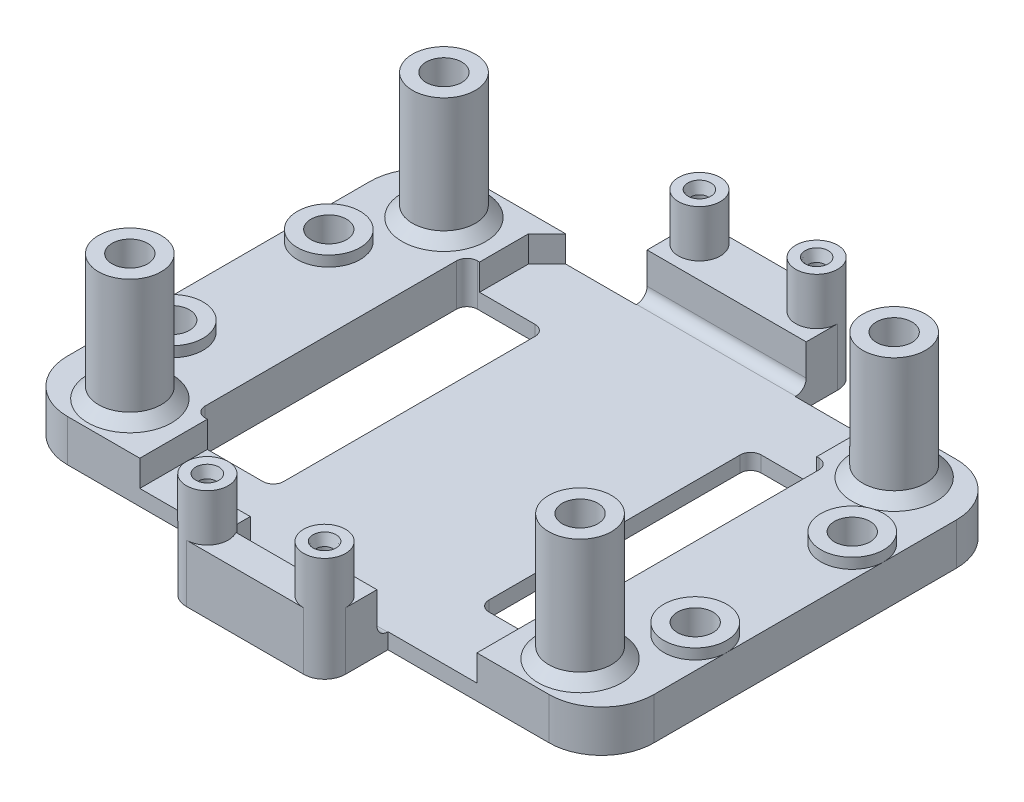
SolidWorks part; units mm, degrees
ref_plane "Front Plane" through (0, 0, 0) normal (0, 0, 1) x (1, 0, 0)
ref_plane "Top Plane" through (0, 0, 0) normal (0, 1, 0) x (1, 0, 0)
ref_plane "Right Plane" through (0, 0, 0) normal (1, 0, 0) x (0, 0, -1)
sketch "Sketch1" plane through (0, 0, 0) normal (0, 1, 0) x (1, 0, 0)
  line L0 (-15.6, 17.4701) -> (-13.6201, 19.45)
  line L1 (-13.6201, 19.45) -> (13.6201, 19.45)
  line L2 (-15.6, 17.4701) -> (-15.6, -19.45)
  line L3 (-15.6, -19.45) -> (15.6, -19.45)
  line L4 (15.6, 17.4701) -> (15.6, -19.45)
  line L5 (-14.7188, 18.3513) -> (15.6, -19.45) construction
  line L6 (-15.6, -19.45) -> (14.7188, 18.3513) construction
  line L7 (-13.6201, 19.45) -> (13.6201, 19.45)
  line L8 (13.6201, 19.45) -> (15.6, 17.4701)
  point P0 (0, 0)
  dimension "D1" = 31.2
  dimension "D2" = 38.9
  dimension "D3" = 45
  dimension "D4" = 2.8
  dimension "D5" = 2.8
  dimension "D6" = 19.45
  dimension "D7" = 15.6
sketch "Sketch2" plane through (0, 0, 0) normal (0, 1, 0) x (1, 0, 0)
  line L1 (-25, 7.5) -> (25, 7.5) construction
  line L2 (-25, 7.5) -> (-25, -7.5) construction
  line L3 (-25, -7.5) -> (25, -7.5) construction
  line L4 (25, 7.5) -> (25, -7.5) construction
  line L5 (-25, 7.5) -> (25, -7.5) construction
  line L6 (-25, -7.5) -> (25, 7.5) construction
  circle A0 centre (-25, 7.5) radius 1.7
  circle A1 centre (-25, -7.5) radius 1.7
  circle A2 centre (25, -7.5) radius 1.7
  circle A3 centre (25, 7.5) radius 1.7
  circle A4 centre (-25, 7.5) radius 3
  circle A5 centre (-25, -7.5) radius 3
  circle A6 centre (25, -7.5) radius 3
  circle A7 centre (25, 7.5) radius 3
  point P0 (0, 0)
  dimension "D3" = 3.4
  dimension "D4" = 6
  dimension "D1" = 50
  dimension "D2" = 15
extrude "Boss-Extrude1" add sketch "Sketch2" along normal blind 5
sketch "Sketch3" plane through (0, 0, 0) normal (0, 1, 0) x (1, 0, 0)
  line L0 (-13.6201, 19.45) -> (13.6201, 19.45) construction
  line L1 (-28, -19.45) -> (28, -19.45)
  line L2 (-28, -19.45) -> (-28, 19.45)
  line L3 (-28, 19.45) -> (28, 19.45)
  line L4 (28, -19.45) -> (28, 19.45)
  line L5 (-28, -19.45) -> (28, 19.45) construction
  line L6 (-28, 19.45) -> (28, -19.45) construction
  circle A0 centre (-25, 7.5) radius 3 construction
  circle A1 centre (-25, 7.5) radius 1.7 construction
  circle A2 centre (-25, 7.5) radius 1.7
  circle A3 centre (25, 7.5) radius 1.7 construction
  circle A4 centre (25, -7.5) radius 1.7 construction
  circle A5 centre (-25, -7.5) radius 1.7 construction
  circle A6 centre (25, 7.5) radius 1.7
  circle A7 centre (25, -7.5) radius 1.7
  circle A8 centre (-25, -7.5) radius 1.7
  point P0 (0, 0)
extrude "Boss-Extrude2" add sketch "Sketch3" along normal blind 4
fillet "Fillet1" radius 5 4 edges at (-28, 2, -19.45) (28, 2, -19.45) (28, 2, 19.45) (-28, 2, 19.45)
extrude "Cut-Extrude2" cut sketch "Sketch1" against normal blind 2.5 from surface contours L8 L1 L0 L2 L3 L4 region at (0, 0, 0.0609) starting at face at (0, 4, -0.75)
sketch "Sketch4" plane through (0, 4, 0) normal (0, 1, 0) x (1, 0, 0)
  line L41 (-16.1, -19.95) -> (16.1, -19.95)
  line L42 (13.8272, 19.95) -> (-13.8272, 19.95)
  line L43 (16.1, -19.95) -> (16.1, 17.6772)
  line L44 (16.1, 17.6772) -> (13.8272, 19.95)
  line L45 (-16.1, 17.6772) -> (-16.1, -19.95)
  line L46 (-13.8272, 19.95) -> (-16.1, 17.6772)
  line L47 (-16.1, -19.95) -> (16.1, -19.95)
  line L48 (13.8272, 19.95) -> (-13.8272, 19.95)
  line L49 (16.1, -19.95) -> (16.1, 17.6772)
  line L50 (16.1, 17.6772) -> (13.8272, 19.95)
  line L51 (-16.1, 17.6772) -> (-16.1, -19.95)
  line L52 (-13.8272, 19.95) -> (-16.1, 17.6772)
  dimension "D1" = 0.5
extrude "Cut-Extrude3" cut sketch "Sketch4" against normal up to surface (2.5 mm away) up to face at (0, 1.5, -5.8234)
sketch "Sketch5" plane through (0, 4, 0) normal (0, 1, 0) x (1, 0, 0)
  line L1 (-21.5, 15) -> (21.5, 15) construction
  line L2 (-21.5, 15) -> (-21.5, -15) construction
  line L3 (-21.5, -15) -> (21.5, -15) construction
  line L4 (21.5, 15) -> (21.5, -15) construction
  line L5 (-21.5, 15) -> (21.5, -15) construction
  line L6 (-21.5, -15) -> (21.5, 15) construction
  circle A0 centre (-21.5, 15) radius 1.7
  circle A1 centre (21.5, 15) radius 1.7
  circle A2 centre (21.5, -15) radius 1.7
  circle A3 centre (-21.5, -15) radius 1.7
  circle A4 centre (-21.5, 15) radius 3
  circle A5 centre (21.5, 15) radius 3
  circle A6 centre (21.5, -15) radius 3
  circle A7 centre (-21.5, -15) radius 3
  point P0 (0, 0)
  dimension "D1" = 3.4
  dimension "D4" = 6
  dimension "D2" = 43
  dimension "D3" = 30
extrude "Boss-Extrude3" add sketch "Sketch5" along normal blind 12
extrude "Cut-Extrude4" cut sketch "Sketch5<2>" against normal through all contours A0 | A3 | A2 | A1
sketch "Sketch5<2>" plane through (0, 4, 0) normal (0, 1, 0) x (1, 0, 0) same geometry as "Sketch5"
sketch "Sketch6" plane through (0, 0, 0) normal (0, -1, 0) x (1, 0, 0)
  line L1 (-19.97, 12.35) -> (-18.44, 15)
  line L2 (-18.44, 15) -> (-19.97, 17.65)
  line L3 (-19.97, 17.65) -> (-23.03, 17.65)
  line L4 (-23.03, 17.65) -> (-24.56, 15)
  line L5 (-24.56, 15) -> (-23.03, 12.35)
  line L6 (-23.03, 12.35) -> (-19.97, 12.35)
  line L7 (23.03, 12.35) -> (24.56, 15)
  line L8 (24.56, 15) -> (23.03, 17.65)
  line L9 (23.03, 17.65) -> (19.97, 17.65)
  line L10 (19.97, 17.65) -> (18.44, 15)
  line L11 (18.44, 15) -> (19.97, 12.35)
  line L12 (19.97, 12.35) -> (23.03, 12.35)
  line L13 (24.56, -15) -> (23.03, -12.35)
  line L14 (23.03, -12.35) -> (19.97, -12.35)
  line L15 (19.97, -12.35) -> (18.44, -15)
  line L16 (18.44, -15) -> (19.97, -17.65)
  line L17 (19.97, -17.65) -> (23.03, -17.65)
  line L18 (23.03, -17.65) -> (24.56, -15)
  line L19 (-18.44, -15) -> (-19.97, -12.35)
  line L20 (-19.97, -12.35) -> (-23.03, -12.35)
  line L21 (-23.03, -12.35) -> (-24.56, -15)
  line L22 (-24.56, -15) -> (-23.03, -17.65)
  line L23 (-23.03, -17.65) -> (-19.97, -17.65)
  line L24 (-19.97, -17.65) -> (-18.44, -15)
  circle A0 centre (-21.5, 15) radius 2.65 construction
  circle A1 centre (21.5, 15) radius 2.65 construction
  circle A2 centre (21.5, -15) radius 2.65 construction
  circle A3 centre (-21.5, -15) radius 2.65 construction
  dimension "D1" = 5.3
extrude "Cut-Extrude5" cut sketch "Sketch6" against normal blind 2.5
chamfer "Chamfer1" distance 1 angle 45 1 edges at (-21.5, 4, 12)
chamfer "Chamfer2" distance 1 angle 45 3 edges at (21.5, 4, 12) (21.5, 4, -18) (-21.5, 4, -18)
sketch "Sketch7" plane through (0, 1.5, 0) normal (0, 1, 0) x (1, 0, 0)
  line L1 (-9.8, -13) -> (-17.3, -13)
  line L2 (-9.8, -13) -> (-9.8, 13)
  line L3 (-9.8, 13) -> (-17.3, 13)
  line L4 (-17.3, -13) -> (-17.3, 13)
  line L5 (-9.8, -13) -> (-17.3, 13) construction
  line L6 (-9.8, 13) -> (-17.3, -13) construction
  line L8 (9.8, -13) -> (17.3, -13)
  line L9 (9.8, -13) -> (9.8, 13)
  line L10 (9.8, 13) -> (17.3, 13)
  line L11 (17.3, -13) -> (17.3, 13)
  line L12 (9.8, -13) -> (17.3, 13) construction
  line L13 (9.8, 13) -> (17.3, -13) construction
  point P0 (-13.55, 0)
  point P7 (13.55, 0)
  dimension "D1" = 7.5
  dimension "D2" = 26
extrude "Cut-Extrude6" cut sketch "Sketch7" against normal through all both and the other way through all
fillet "Fillet3" radius 1 8 edges at (-17.3, 2, 13) (-9.8, 0.75, 13) (-17.3, 2, -13) (-9.8, 0.75, -13) (9.8, 0.75, 13) (17.3, 2, 13) (9.8, 0.75, -13) (17.3, 2, -13)
sketch "Sketch8" plane through (0, 0, 0) normal (0, 1, 0) x (1, 0, 0)
  line L0 (-5.6, -23.5) -> (5.6, -23.5) construction
  line L1 (-5.6, -23.5) -> (-5.6, 23.5) construction
  line L2 (-5.6, 23.5) -> (5.6, 23.5) construction
  line L3 (5.6, -23.5) -> (5.6, 23.5) construction
  line L4 (-5.6, -23.5) -> (5.6, 23.5) construction
  line L5 (-5.6, 23.5) -> (5.6, -23.5) construction
  circle A0 centre (-5.6, 23.5) radius 0.8
  circle A1 centre (5.6, 23.5) radius 0.8
  circle A2 centre (5.6, -23.5) radius 0.8
  circle A3 centre (-5.6, -23.5) radius 0.8
  circle A4 centre (-5.6, 23.5) radius 2
  circle A5 centre (5.6, 23.5) radius 2
  circle A6 centre (-5.6, -23.5) radius 2
  circle A7 centre (5.6, -23.5) radius 2
  point P0 (0, 0)
  dimension "D1" = 1.6
  dimension "D2" = 4
  dimension "D3" = 11.2
  dimension "D4" = 47
extrude "Boss-Extrude4" add sketch "Sketch8" along normal blind 10 separate body
sketch "Sketch9" plane through (0, 0, 0) normal (0, 1, 0) x (1, 0, 0)
  line L0 (-5.6, -25.5) -> (5.6, -25.5)
  line L1 (-7.6, -23.5) -> (-7.6, 23.5)
  line L2 (-5.6, 25.5) -> (5.6, 25.5)
  line L3 (7.6, -23.5) -> (7.6, 23.5)
  line L4 (-6.852, -25.0597) -> (6.852, 25.0597) construction
  line L5 (-6.8645, 21.9504) -> (7.522, -24.0531) construction
  arc A0 (5.6, -25.5) -> (7.6, -23.5) centre (5.6, -23.5) ccw
  arc A1 (-7.6, -23.5) -> (-5.6, -25.5) centre (-5.6, -23.5) ccw
  arc A2 (7.6, 23.5) -> (5.6, 25.5) centre (5.6, 23.5) ccw
  arc A3 (-5.6, 25.5) -> (-7.6, 23.5) centre (-5.6, 23.5) ccw
  circle A4 centre (-5.6, 23.5) radius 2 construction
  circle A5 centre (5.6, 23.5) radius 2 construction
  circle A6 centre (-5.6, -23.5) radius 2 construction
  circle A7 centre (5.6, -23.5) radius 2 construction
  point P0 (0, 0)
extrude "Boss-Extrude5" add sketch "Sketch9" along normal up to surface (1.5 mm away) up to face at (0, 1.5, -1.9641)
sketch "Sketch10" plane through (0, 1.5, 0) normal (0, 1, 0) x (1, 0, 0)
  line L0 (7.6, 23.5) -> (7.6, 19.45) construction
  line L1 (-7.6, 19.45) -> (-7.6, 23.5) construction
  line L2 (-5.6, 25.5) -> (5.6, 25.5) construction
  line L3 (7.6, 23.5) -> (7.6, 20.5)
  line L4 (-7.6, 20.5) -> (-7.6, 23.5)
  line L5 (-5.6, 25.5) -> (5.6, 25.5)
  line L6 (-7.6, 20.5) -> (7.6, 20.5)
  line L7 (-1000.2677, 0) -> (48999.7323, 0) construction
  line L9 (-5.6, -25.5) -> (5.6, -25.5)
  line L10 (-7.6, -20.5) -> (-7.6, -23.5)
  line L11 (7.6, -23.5) -> (7.6, -20.5)
  line L12 (-7.6, -20.5) -> (-4.5, -20.5)
  line L13 (-4.5, -22.5) -> (4.5, -22.5)
  line L14 (-4.5, -22.5) -> (-4.5, -20.5)
  line L16 (4.5, -22.5) -> (4.5, -20.5)
  line L17 (-4.5, -22.5) -> (4.5, -20.5) construction
  line L18 (-4.5, -20.5) -> (4.5, -22.5) construction
  line L19 (4.5, -20.5) -> (7.6, -20.5)
  circle A0 centre (-5.6, 23.5) radius 2 construction
  circle A1 centre (5.6, 23.5) radius 2 construction
  arc A2 (-5.6, 25.5) -> (-7.6, 23.5) centre (-5.6, 23.5) ccw
  arc A3 (7.6, 23.5) -> (5.6, 25.5) centre (5.6, 23.5) ccw
  arc A4 (7.6, -23.5) -> (5.6, -25.5) centre (5.6, -23.5) cw
  arc A5 (-5.6, -25.5) -> (-7.6, -23.5) centre (-5.6, -23.5) cw
  point P23 (0, -21.5)
  dimension "D1" = 5
  dimension "D2" = 2
  dimension "D3" = 9
extrude "Boss-Extrude7" add sketch "Sketch10" along normal blind 4
fillet "Fillet4" radius 1 4 edges at (0, 1.5, -20.5) (0, 1.5, 22.5) (-6.05, 1.5, 20.5) (6.05, 1.5, 20.5)
extrude "Cut-Extrude9" cut sketch "Sketch8<2>" along normal through all both and the other way through all contours A0 | A3 | A2 | A1 | A0 region at (-5.6, 0, -23.5)
sketch "Sketch8<2>" plane through (0, 0, 0) normal (0, 1, 0) x (1, 0, 0) same geometry as "Sketch8"
chamfer "Chamfer3" distance 0.3 distance2 1 4 edges at (-5.6, 10, 24.3) (5.6, 10, 24.3) (-5.6, 10, -22.7) (5.6, 10, -22.7) first distance on face at (-5.6, 10, 25.5) first distance on face at (5.6, 10, 25.5) first distance on face at (-5.6, 10, -21.5) first distance on face at (5.6, 10, -21.5)
